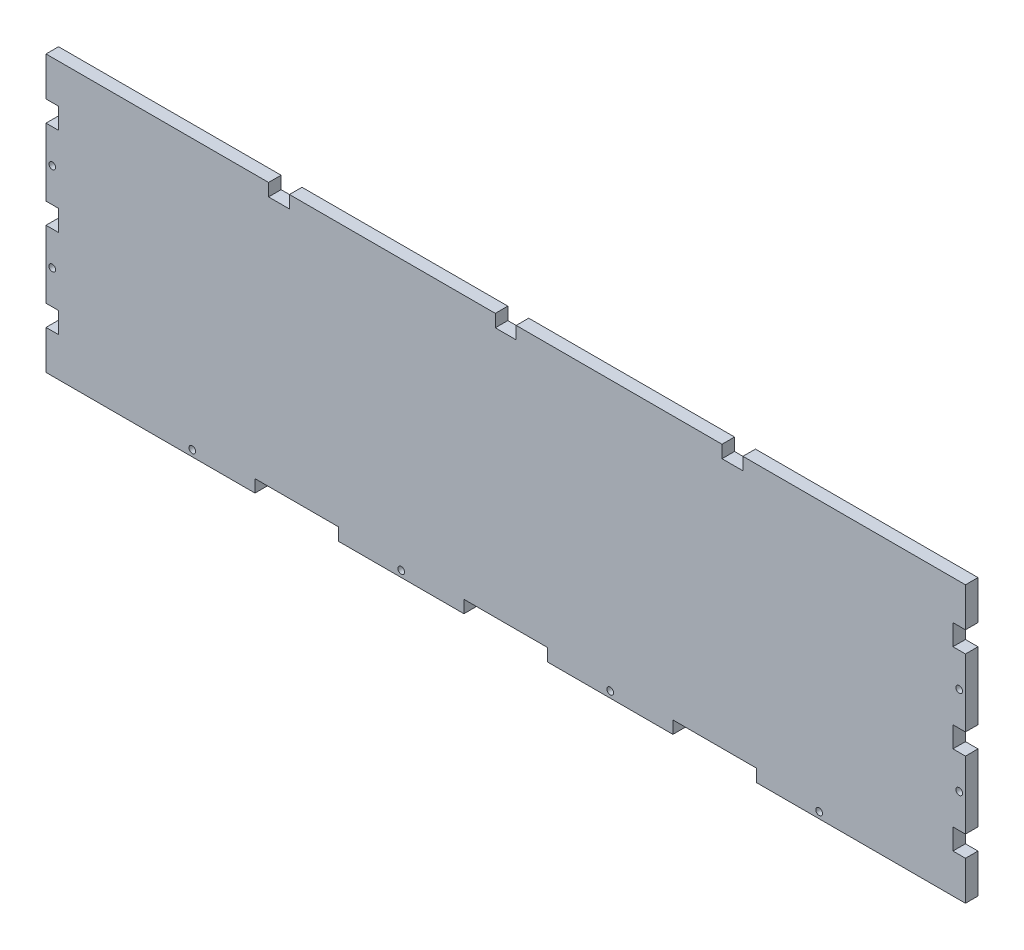
SolidWorks part; units mm, degrees
ref_plane "Front Plane" through (0, 0, 0) normal (0, 0, 1) x (1, 0, 0)
ref_plane "Top Plane" through (0, 0, 0) normal (0, 1, 0) x (1, 0, 0)
ref_plane "Right Plane" through (0, 0, 0) normal (1, 0, 0) x (0, 0, -1)
sketch "Sketch1" plane through (0, 0, 0) normal (0, 0, 1) x (1, 0, 0)
  line L1 (-220, -66) -> (220, -66)
  line L2 (-220, -66) -> (-220, 66)
  line L3 (-220, 66) -> (220, 66)
  line L4 (220, -66) -> (220, 66)
  line L5 (-220, -66) -> (220, 66) construction
  line L6 (-220, 66) -> (220, -66) construction
  point P0 (0, 0)
  dimension "D1" = 440
  dimension "D2" = 132
extrude "Boss-Extrude1" add sketch "Sketch1" along normal blind 6
sketch "Sketch2" plane through (0, 0, 0) normal (0, 0, -1) x (-1, 0, 0)
  line L0 (220, 47.3321) -> (220, 37.3321) construction
  line L1 (220, 37.3321) -> (214, 37.3321) construction
  line L2 (214, 37.3321) -> (214, 47.3321) construction
  line L3 (214, 47.3321) -> (220, 47.3321) construction
  line L12 (220, -37.3321) -> (220, -47.3321) construction
  line L13 (220, -47.3321) -> (214, -47.3321) construction
  line L14 (214, -47.3321) -> (214, -37.3321) construction
  line L15 (214, -37.3321) -> (220, -37.3321) construction
  line L16 (220, 47.3321) -> (220, 37.3321)
  line L17 (220, 37.3321) -> (214, 37.3321)
  line L18 (214, 37.3321) -> (214, 47.3321)
  line L19 (214, 47.3321) -> (220, 47.3321)
  line L20 (220, -37.3321) -> (220, -47.3321)
  line L21 (220, -47.3321) -> (214, -47.3321)
  line L22 (214, -47.3321) -> (214, -37.3321)
  line L23 (214, -37.3321) -> (220, -37.3321)
  line L24 (-214, -37.3321) -> (-214, -47.3321) construction
  line L25 (-214, -47.3321) -> (-220, -47.3321) construction
  line L26 (-220, -47.3321) -> (-220, -37.3321) construction
  line L27 (-220, -37.3321) -> (-214, -37.3321) construction
  line L28 (-214, 47.3321) -> (-214, 37.3321) construction
  line L29 (-214, 37.3321) -> (-220, 37.3321) construction
  line L30 (-220, 37.3321) -> (-220, 47.3321) construction
  line L31 (-220, 47.3321) -> (-214, 47.3321) construction
  line L32 (-214, -37.3321) -> (-214, -47.3321)
  line L33 (-214, -47.3321) -> (-220, -47.3321)
  line L34 (-220, -47.3321) -> (-220, -37.3321)
  line L35 (-220, -37.3321) -> (-214, -37.3321)
  line L36 (-214, 47.3321) -> (-214, 37.3321)
  line L37 (-214, 37.3321) -> (-220, 37.3321)
  line L38 (-220, 37.3321) -> (-220, 47.3321)
  line L39 (-220, 47.3321) -> (-214, 47.3321)
  line L44 (220, -5) -> (220, 5)
  line L45 (214, -5) -> (220, -5)
  line L46 (214, 5) -> (214, -5)
  line L47 (220, 5) -> (214, 5)
  line L48 (220, -5) -> (220, 5)
  line L49 (214, -5) -> (220, -5)
  line L50 (214, 5) -> (214, -5)
  line L51 (220, 5) -> (214, 5)
  line L52 (-214, -5) -> (-214, 5)
  line L53 (-220, -5) -> (-214, -5)
  line L54 (-220, 5) -> (-220, -5)
  line L55 (-214, 5) -> (-220, 5)
  line L56 (-214, -5) -> (-214, 5)
  line L57 (-220, -5) -> (-214, -5)
  line L58 (-220, 5) -> (-220, -5)
  line L59 (-214, 5) -> (-220, 5)
  circle A0 centre (217, 21.1661) radius 1.6 construction
  circle A1 centre (217, -21.1661) radius 1.6 construction
  circle A2 centre (-217, 21.1661) radius 1.6 construction
  circle A3 centre (-217, -21.1661) radius 1.6 construction
  circle A4 centre (217, 21.1661) radius 1.6
  circle A5 centre (217, -21.1661) radius 1.6
  circle A6 centre (-217, 21.1661) radius 1.6
  circle A7 centre (-217, -21.1661) radius 1.6
  dimension "D2" = 0
  dimension "D3" = 0
extrude "Cut-Extrude1" cut sketch "Sketch2" against normal up to next
sketch "Sketch3" plane through (0, 0, 0) normal (0, 0, -1) x (-1, 0, 0)
  circle A0 centre (-150, -63) radius 1.6 construction
  circle A1 centre (-50, -63) radius 1.6 construction
  circle A2 centre (50, -63) radius 1.6 construction
  circle A3 centre (150, -63) radius 1.6 construction
  circle A4 centre (-150, -63) radius 1.6
  circle A5 centre (-50, -63) radius 1.6
  circle A6 centre (50, -63) radius 1.6
  circle A7 centre (150, -63) radius 1.6
extrude "Cut-Extrude2" cut sketch "Sketch3" against normal up to next
sketch "Sketch4" plane through (0, 0, 0) normal (0, 0, -1) x (-1, 0, 0)
  line L0 (80, -66) -> (120, -66) construction
  line L1 (120, -66) -> (120, -60) construction
  line L2 (120, -60) -> (80, -60) construction
  line L3 (80, -60) -> (80, -66) construction
  line L4 (-20, -66) -> (20, -66) construction
  line L5 (20, -66) -> (20, -60) construction
  line L6 (20, -60) -> (-20, -60) construction
  line L7 (-20, -60) -> (-20, -66) construction
  line L8 (-120, -66) -> (-80, -66) construction
  line L9 (-80, -66) -> (-80, -60) construction
  line L10 (-80, -60) -> (-120, -60) construction
  line L11 (-120, -60) -> (-120, -66) construction
  line L12 (80, -66) -> (120, -66)
  line L13 (120, -66) -> (120, -60)
  line L14 (120, -60) -> (80, -60)
  line L15 (80, -60) -> (80, -66)
  line L16 (-20, -66) -> (20, -66)
  line L17 (20, -66) -> (20, -60)
  line L18 (20, -60) -> (-20, -60)
  line L19 (-20, -60) -> (-20, -66)
  line L20 (-120, -66) -> (-80, -66)
  line L21 (-80, -66) -> (-80, -60)
  line L22 (-80, -60) -> (-120, -60)
  line L23 (-120, -60) -> (-120, -66)
extrude "Cut-Extrude3" cut sketch "Sketch4" against normal up to next
sketch "Sketch5" plane through (0, 66, 0) normal (0, 1, 0) x (1, 0, 0)
  line L0 (220, 0) -> (-220, 0) construction
  line L1 (-113.5, -6) -> (-103.5, -6)
  line L2 (-113.5, -6) -> (-113.5, 0)
  line L3 (-113.5, 0) -> (-103.5, 0)
  line L4 (-103.5, -6) -> (-103.5, 0)
  line L5 (-113.5, -6) -> (-103.5, 0) construction
  line L6 (-113.5, 0) -> (-103.5, -6) construction
  line L7 (-103.5, -6) -> (-103.5, 0) construction
  line L8 (5, -6) -> (5, 0) construction
  line L9 (-5, -6) -> (5, -6)
  line L10 (-5, -6) -> (-5, 0)
  line L11 (-5, 0) -> (5, 0)
  line L12 (5, -6) -> (5, 0)
  line L13 (-5, -6) -> (5, 0) construction
  line L14 (-5, 0) -> (5, -6) construction
  line L15 (113.5, -6) -> (113.5, 0) construction
  line L16 (103.5, -6) -> (113.5, -6)
  line L17 (103.5, -6) -> (103.5, 0)
  line L18 (103.5, 0) -> (113.5, 0)
  line L19 (113.5, -6) -> (113.5, 0)
  line L20 (103.5, -6) -> (113.5, 0) construction
  line L21 (103.5, 0) -> (113.5, -6) construction
  point P0 (-108.5, -3)
  point P10 (0, -3)
  point P18 (108.5, -3)
extrude "Cut-Extrude4" cut sketch "Sketch5" against normal blind 6
